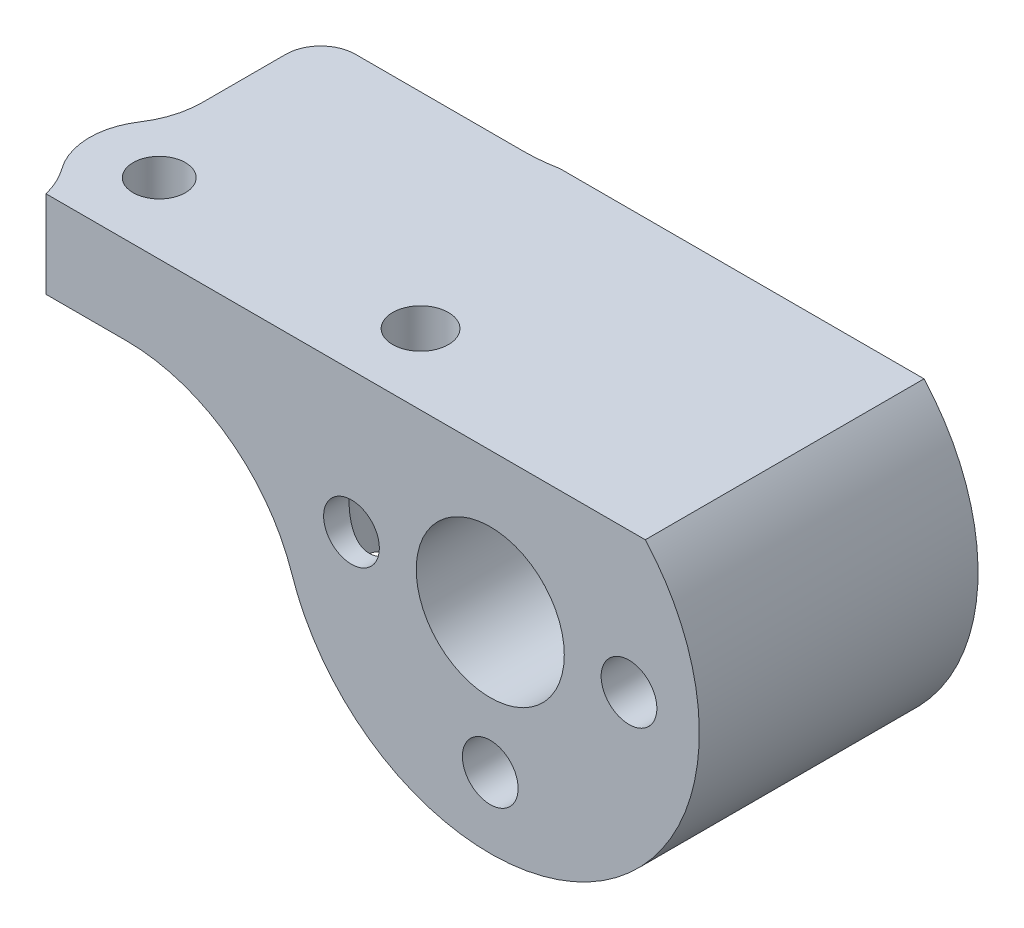
SolidWorks part; units mm, degrees
material "Thornel Mat VMA"
ref_plane "Plano frontal" through (0, 0, 0) normal (0, 0, 1) x (1, 0, 0)
ref_plane "Plano superior" through (0, 0, 0) normal (0, 1, 0) x (1, 0, 0)
ref_plane "Plano direito" through (0, 0, 0) normal (1, 0, 0) x (0, 0, -1)
sketch "Esboço1" plane through (0, 0, 0) normal (0, 0, 1) x (1, 0, 0)
  line L0 (115.6466, -302.7659) -> (115.6466, -295.7159)
  line L1 (92.6466, -295.7159) -> (114.6466, -295.7159) construction
  line L2 (91.6466, -302.7659) -> (91.6466, -295.7159)
  line L3 (92.6466, -302.7659) -> (92.6466, -295.7159) construction
  line L4 (91.6466, -295.7159) -> (115.6466, -295.7159)
  line L5 (114.6466, -302.7659) -> (114.6466, -295.7159) construction
  line L6 (91.6466, -294.7159) -> (115.6466, -294.7159) construction
  line L7 (91.6466, -302.7659) -> (91.6466, -294.7159) construction
  line L8 (115.6466, -302.7659) -> (115.6466, -294.7159) construction
  circle A0 centre (103.6466, -302.7659) radius 7.9647 construction
  arc A1 (92.6466, -302.7659) -> (114.6466, -302.7659) centre (103.6466, -302.7659) ccw construction
  arc A2 (91.6466, -302.7659) -> (115.6466, -302.7659) centre (103.6466, -302.7659) ccw
  dimension "D1" = 11
  dimension "D2" = 1
extrude "Ressalto-extrusão1" add sketch "Esboço1" along normal blind 10 and the other way blind 6
sketch "Sketch4" [suppressed] plane through (0, 0, 9) normal (0, 0, 1) x (1, 0, 0)
  line L1 (92.6466, -295.7159) -> (114.6466, -295.7159)
  line L2 (92.6466, -295.7159) -> (92.6466, -299.8338)
  line L3 (92.6466, -299.8338) -> (114.6466, -299.8338)
  line L4 (114.6466, -295.7159) -> (114.6466, -299.8338)
sketch "Esboço2" plane through (0, 0, 10) normal (0, 0, 1) x (1, 0, 0)
  circle A0 centre (103.6466, -302.7659) radius 5.25
  dimension "10.5" = 10.5
extrude "Corte-extrusão1" cut sketch "Esboço2" against normal blind 31.8 and the other way blind 16
ref_plane "Plane1" through (0, -314.7159, 0) normal (0, 1, 0) x (1, 0, 0)
sketch "Sketch8" plane through (0, 0, 10) normal (0, 0, 1) x (1, 0, 0)
  line L3 (115.6466, -295.7159) -> (91.6466, -295.7159)
  line L4 (115.6466, -295.7159) -> (91.6466, -295.7159)
  line L5 (115.6466, -302.7659) -> (115.6466, -295.7159)
  line L6 (115.6466, -302.7659) -> (115.6466, -295.7159)
  line L7 (91.6466, -295.7159) -> (91.6466, -302.7659)
  line L8 (91.6466, -295.7159) -> (91.6466, -302.7659)
  arc A1 (91.6466, -302.7659) -> (115.6466, -302.7659) centre (103.6466, -302.7659) ccw
  arc A2 (91.6466, -302.7659) -> (115.6466, -302.7659) centre (103.6466, -302.7659) ccw
  dimension "D1" = 0
extrude "Boss-Extrude2" [suppressed] add sketch "Sketch8" along normal blind 5
hole_wizard "M3 Clearance Hole5" positions "Sketch10" profile "Sketch9" hole size "M3" standard "ISO" end condition through all
sketch "Sketch10" plane through (0, 0, 10) normal (0, 0, 1) x (1, 0, 0)
  point P0 (95.6819, -302.7659)
  point P2 (103.6466, -310.7307)
  point P4 (111.6113, -302.7659)
sketch "Sketch9" plane through (95.6819, -302.7659, 10) normal (1, 0, 0) x (0, -1, 0)
  line L0 (0, 0) -> (0, 16)
  line L1 (0, 16) -> (1.6, 16)
  line L2 (1.6, 16) -> (1.6, 0)
  line L5 (1.6, 0) -> (0, 0)
  line L11 (0, -6.35) -> (0, 107.95) construction
  dimension "Thru Hole Dia." = 3.2
  dimension "Thru Hole Depth" = 16
hole_wizard "CBORE for M5 Hex Head Bolt1" positions "Sketch6" profile "Sketch5" counterbore size "M5" standard "DIN" end condition through all
sketch "Sketch6" plane through (0, -314.7159, 0) normal (0, -1, 0) x (-1, 0, 0)
  point P0 (-95.5966, -5.9493)
  point P8 (0, 0)
  point P9 (0, 0)
sketch "Sketch5" plane through (95.5966, -314.7159, 5.9493) normal (1, 0, 0) x (0, 0, -1)
  line L0 (0, 0) -> (0, 19)
  line L1 (0, 19) -> (1.6, 19)
  line L3 (1.6, 19) -> (1.6, 16.5)
  line L4 (1.6, 16.5) -> (3, 16.5)
  line L5 (3, 16.5) -> (3, 0)
  line L7 (3, 0) -> (0, 0)
  line L11 (0, -6.35) -> (0, 107.95) construction
  dimension "Thru Hole Dia." = 3.2
  dimension "Thru Hole Depth" = 19
  dimension "C'Bore Dia." = 6
  dimension "C'Bore Depth" = 16.5
sketch "Sketch11" plane through (0, -295.7159, 0) normal (0, 1, 0) x (1, 0, 0)
  line L4 (115.6466, 6) -> (91.6466, 6)
  line L5 (91.6466, 6) -> (91.6466, -10)
  line L6 (91.6466, -10) -> (115.6466, -10)
  line L7 (115.6466, -10) -> (115.6466, 6)
  line L8 (115.6466, 6) -> (91.6466, 6)
  line L9 (91.6466, 6) -> (91.6466, -10)
  line L10 (91.6466, -10) -> (115.6466, -10)
  line L11 (115.6466, -10) -> (115.6466, 6)
  circle A0 centre (95.5966, -5.9493) radius 1.6 construction
  circle A2 centre (95.5966, -5.9493) radius 1.6
  dimension "D1" = 0
extrude "Boss-Extrude3" add sketch "Sketch11" along normal blind 1
sketch "Esboço3" plane through (0, -294.7159, 0) normal (0, -1, 0) x (1, 0, 0)
  line L0 (78.0966, 0.9744) -> (78.0966, -3.8157) construction
  line L1 (91.6466, 10) -> (78.1471, 10)
  line L2 (91.6466, 10) -> (91.6466, -5.8157)
  line L3 (91.6466, -5.8157) -> (80.0966, -5.8157)
  line L5 (78.0966, 0.9744) -> (78.0966, -3.8157)
  arc A0 (78.0966, -3.8157) -> (80.0966, -5.8157) centre (80.0966, -3.8157) ccw construction
  arc A1 (78.0966, 0.9744) -> (77.2633, 3.7383) centre (73.0966, 0.9744) ccw construction
  arc A2 (77.3521, 8.2889) -> (78.2966, 11.2134) centre (73.2966, 11.2134) ccw construction
  arc A3 (77.3521, 8.2889) -> (77.2633, 3.7383) centre (80.5966, 5.9493) ccw construction
  arc A4 (78.0966, -3.8157) -> (80.0966, -5.8157) centre (80.0966, -3.8157) ccw
  arc A5 (78.0966, 0.9744) -> (77.2633, 3.7383) centre (73.0966, 0.9744) ccw
  arc A6 (77.3521, 8.2889) -> (78.1471, 10) centre (73.2966, 11.2134) ccw
  arc A7 (77.3521, 8.2889) -> (77.2633, 3.7383) centre (80.5966, 5.9493) ccw
extrude "Ressalto-extrusão2" add sketch "Esboço3" along normal blind 5
sketch "Sketch12" plane through (0, 0, 10) normal (0, 0, 1) x (1, 0, 0)
  circle A1 centre (103.6466, -302.7659) radius 5.25
  circle A2 centre (103.6466, -302.7659) radius 4.25
extrude "Boss-Extrude5" add sketch "Sketch12" against normal blind 6
chamfer "Chamfer1" distance 0.3 angle 45 1 edges at (108.8966, -302.7659, -6)
sketch "Sketch13" plane through (0, -298.2159, 0) normal (0, -1, 0) x (1, 0, 0)
  circle A0 centre (95.5966, 5.9493) radius 3 construction
  circle A1 centre (95.5966, 5.9493) radius 3
extrude "Cut-Extrude1" cut sketch "Sketch13" along normal blind 43.8
fillet "Filete1" radius 10 1 edges at (91.6466, -299.7159, 2.0921)
fillet "Filete2" radius 10 2 edges at (91.8012, -304.6861, -5.8157) (91.6466, -298.7409, -5.8157)
sketch "Esboço4" plane through (0, 0, 10) normal (0, 0, 1) x (1, 0, 0)
  line L0 (115.6466, -302.7659) -> (115.6466, -294.7159) construction
  line L2 (115.6466, -302.7659) -> (115.6466, -294.7159)
  line L4 (112.5459, -294.7159) -> (115.6466, -294.7159)
  arc A0 (115.6466, -302.7659) -> (112.5459, -294.7159) centre (103.6466, -302.7659) ccw
extrude "Corte-extrusão2" cut sketch "Esboço4" against normal blind 23
hole_wizard "Furo de diâmetro Ø3.0 (3)1" positions "Esboço5" profile "Esboço6" hole size "Ø3.0" standard "ISO"
sketch "Esboço5" plane through (0, -299.7159, 0) normal (0, -1, 0) x (-1, 0, 0)
  point P0 (-80.5966, -5.9493)
sketch "Esboço6" plane through (80.5966, -299.7159, 5.9493) normal (1, 0, 0) x (0, 0, -1)
  line L0 (0, 0) -> (0, 5.9013)
  line L1 (0, 5.9013) -> (1.5, 5)
  line L2 (1.5, 5) -> (1.5, 0)
  line L5 (1.5, 0) -> (0, 0)
  line L10 (0, 5.9013) -> (-1.5, 5) construction
  line L11 (0, -6.35) -> (0, 107.95) construction
  dimension "Hole Dia." = 3
  dimension "Hole Depth" = 5
  dimension "Drill Angle" = 118
sketch "Esboço7" plane through (0, -299.7159, 0) normal (0, -1, 0) x (-1, 0, 0)
  circle A0 centre (-80.5966, -5.9493) radius 3
  dimension "D1" = 6
extrude "Corte-extrusão3" cut sketch "Esboço7" along normal blind 13
